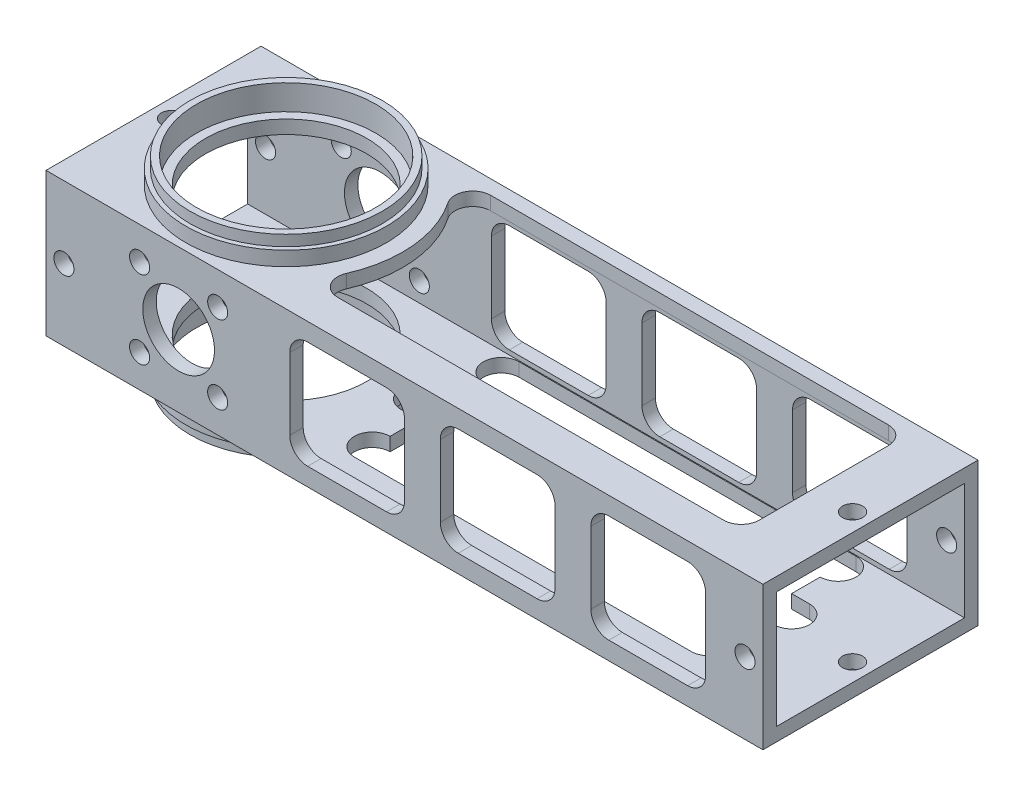
SolidWorks part; units mm, degrees
material "6061 Alloy"
ref_plane "Front Plane" through (0, 0, 0) normal (0, 0, 1) x (1, 0, 0)
ref_plane "Top Plane" through (0, 0, 0) normal (0, 1, 0) x (1, 0, 0)
ref_plane "Right Plane" through (0, 0, 0) normal (1, 0, 0) x (0, 0, -1)
sketch "Sketch1" plane through (0, 0, 0) normal (1, 0, 0) x (0, 0, -1)
  line L0 (2.3813, 23.0187) -> (35.7188, 23.0187)
  line L1 (0, 0) -> (38.1, 0)
  line L2 (0, 0) -> (0, 25.4)
  line L3 (0, 25.4) -> (38.1, 25.4)
  line L4 (38.1, 0) -> (38.1, 25.4)
  line L5 (35.7188, 2.3813) -> (35.7188, 23.0187)
  line L6 (2.3813, 2.3813) -> (35.7188, 2.3813)
  line L7 (2.3813, 2.3813) -> (2.3813, 23.0187)
  dimension "D1" = 38.1
  dimension "D2" = 25.4
  dimension "D3" = 2.3813
extrude "Boss-Extrude1" add sketch "Sketch1" along normal blind 127
sketch "Sketch2" plane through (0, 25.4, 0) normal (0, 1, 0) x (1, 0, 0)
  line L0 (0, 19.05) -> (23.495, 19.05) construction
  line L1 (0, 38.1) -> (0, 0) construction
  circle A0 centre (23.495, 19.05) radius 14.2875
  dimension "D2" = 28.575
  dimension "D1" = 23.495
extrude "Cut-Extrude1" cut sketch "Sketch2" against normal through all
sketch "Sketch3" plane through (0, 0, 0) normal (0, 0, 1) x (1, 0, 0)
  line L0 (0, 12.7) -> (23.495, 12.7) construction
  line L1 (0, 25.4) -> (0, 0) construction
  line L2 (0, 25.4) -> (23.495, 25.4) construction
  line L3 (63.5, 22.225) -> (69.85, 22.225) construction
  line L4 (16.5802, 5.7852) -> (30.4098, 5.7852) construction
  line L5 (16.5802, 5.7852) -> (16.5802, 19.6148) construction
  line L6 (16.5802, 19.6148) -> (30.4098, 19.6148) construction
  line L7 (30.4098, 5.7852) -> (30.4098, 19.6148) construction
  line L8 (16.5802, 5.7852) -> (30.4098, 19.6148) construction
  line L9 (16.5802, 19.6148) -> (30.4098, 5.7852) construction
  line L10 (46.355, 22.225) -> (60.325, 22.225)
  line L11 (43.18, 19.05) -> (43.18, 6.35)
  line L12 (46.355, 3.175) -> (60.325, 3.175)
  line L13 (63.5, 19.05) -> (63.5, 6.35)
  line L14 (73.025, 22.225) -> (86.995, 22.225)
  line L15 (69.85, 19.05) -> (69.85, 6.35)
  line L16 (73.025, 3.175) -> (86.995, 3.175)
  line L17 (90.17, 19.05) -> (90.17, 6.35)
  line L18 (99.695, 22.225) -> (113.665, 22.225)
  line L19 (96.52, 19.05) -> (96.52, 6.35)
  line L20 (99.695, 3.175) -> (113.665, 3.175)
  line L21 (116.84, 19.05) -> (116.84, 6.35)
  line L22 (90.17, 22.225) -> (96.52, 22.225) construction
  line L23 (127, 12.7) -> (116.84, 12.7) construction
  line L24 (127, 25.4) -> (127, 0) construction
  circle A0 centre (23.495, 12.7) radius 6.35
  circle A1 centre (16.5802, 19.6148) radius 1.778
  circle A2 centre (16.5802, 5.7852) radius 1.778
  circle A3 centre (30.4098, 5.7852) radius 1.778
  circle A4 centre (30.4098, 19.6148) radius 1.778
  arc A5 (113.665, 22.225) -> (116.84, 19.05) centre (113.665, 19.05) cw
  arc A6 (113.665, 3.175) -> (116.84, 6.35) centre (113.665, 6.35) ccw
  arc A7 (96.52, 6.35) -> (99.695, 3.175) centre (99.695, 6.35) ccw
  arc A8 (99.695, 22.225) -> (96.52, 19.05) centre (99.695, 19.05) ccw
  arc A9 (86.995, 22.225) -> (90.17, 19.05) centre (86.995, 19.05) cw
  arc A10 (86.995, 3.175) -> (90.17, 6.35) centre (86.995, 6.35) ccw
  arc A11 (69.85, 6.35) -> (73.025, 3.175) centre (73.025, 6.35) ccw
  arc A12 (73.025, 22.225) -> (69.85, 19.05) centre (73.025, 19.05) ccw
  arc A13 (60.325, 22.225) -> (63.5, 19.05) centre (60.325, 19.05) cw
  arc A14 (60.325, 3.175) -> (63.5, 6.35) centre (60.325, 6.35) ccw
  arc A15 (43.18, 6.35) -> (46.355, 3.175) centre (46.355, 6.35) ccw
  arc A16 (46.355, 22.225) -> (43.18, 19.05) centre (46.355, 19.05) ccw
  point P33 (116.84, 22.225)
  point P36 (116.84, 3.175)
  dimension "D1" = 12.7
  dimension "D3" = 3.556
  dimension "D8" = 3.175
  dimension "D2" = 19.558
  dimension "D4" = 20.32
  dimension "D5" = 19.05
  dimension "D6" = 6.35
  dimension "D7" = 10.16
extrude "Cut-Extrude2" cut sketch "Sketch3" against normal through all
sketch "Sketch4" plane through (0, 25.4, 0) normal (0, 1, 0) x (1, 0, 0)
  line L0 (45.3195, 6.35) -> (113.665, 6.35)
  line L1 (116.84, 9.525) -> (116.84, 32.385)
  line L2 (113.665, 35.56) -> (43.2235, 35.56)
  line L3 (116.84, 19.05) -> (127, 19.05) construction
  line L4 (127, 38.1) -> (127, 0) construction
  line L5 (127, 0) -> (116.84, 0) construction
  line L6 (127, 38.1) -> (0, 38.1) construction
  line L7 (127, 0) -> (0, 0) construction
  line L8 (79.4923, 6.35) -> (79.4923, 35.56) construction
  arc A0 (42.4096, 10.795) -> (40.593, 30.607) centre (23.495, 19.05) ccw
  circle A1 centre (23.495, 19.05) radius 14.2875 construction
  arc A2 (113.665, 6.35) -> (116.84, 9.525) centre (113.665, 9.525) ccw
  arc A3 (116.84, 32.385) -> (113.665, 35.56) centre (113.665, 32.385) ccw
  arc A4 (40.593, 30.607) -> (43.2235, 35.56) centre (43.2235, 32.385) cw
  arc A5 (42.4096, 10.795) -> (45.3195, 6.35) centre (45.3195, 9.525) ccw
  dimension "D3" = 6.35
  dimension "D4" = 3.175
  dimension "D1" = 2.54
  dimension "D2" = 6.35
extrude "Cut-Extrude3" cut sketch "Sketch4" against normal up to next
hole_wizard "#4 (0.209) Diameter Hole1" positions "3DSketch1" profile "Sketch5" hole size "#4" standard "ANSI Inch" end condition up to next
sketch3d "3DSketch1"
  line L0 (127, 25.4, -19.05) -> (123.825, 25.4, -19.05) construction
  line L1 (127, 25.4, -38.1) -> (127, 25.4, 0) construction
  line L6 (127, 12.7, 0) -> (123.825, 12.7, 0) construction
  line L7 (127, 25.4, 0) -> (127, 0, 0) construction
  line L13 (0, 25.4, -19.05) -> (3.175, 25.4, -19.05) construction
  line L14 (0, 25.4, -38.1) -> (0, 25.4, 0) construction
  line L17 (0, 12.7, 0) -> (3.175, 12.7, 0) construction
  line L18 (0, 25.4, 0) -> (0, 0, 0) construction
  point P13 (123.825, 12.7, 0)
  point P24 (3.175, 25.4, -19.05)
  point P30 (3.175, 12.7, 0)
  point P48 (3.175, 25.4, -19.05)
  point P67 (3.175, 25.4, -19.05)
  point P69 (3.175, 12.7, 0)
  point P77 (123.825, 25.4, -19.05)
  point P79 (123.825, 12.7, 0)
  point P81 (123.825, 0, -19.05)
  point P83 (123.825, 12.7, -38.1)
  point P90 (3.175, 12.7, -38.1)
  point P92 (3.175, 0, -19.05)
  dimension "D1" = 3.175
sketch "Sketch5" plane through (3.175, 25.4, -19.05) normal (1, 0, 0) x (0, 0, 1)
  line L0 (0, 0) -> (0, 2.3822)
  line L1 (0, 2.3822) -> (1.778, 2.3822)
  line L2 (1.778, 2.3822) -> (1.778, 0)
  line L5 (1.778, 0) -> (0, 0)
  line L11 (0, -6.35) -> (0, 107.95) construction
  dimension "Thru Hole Dia." = 3.556
  dimension "Thru Hole Depth" = 2.3823
sketch "Sketch6" plane through (0, 0, 0) normal (0, -1, 0) x (1, 0, 0)
  line L0 (48.26, -35.56) -> (107.95, -35.56)
  line L1 (48.26, -6.35) -> (107.95, -6.35)
  line L2 (79.4923, -6.35) -> (79.4923, -35.56) construction
  line L3 (113.665, -35.56) -> (43.2235, -35.56) construction
  line L4 (127, 0) -> (127, -38.1) construction
  line L5 (48.26, -6.35) -> (48.26, -35.56) construction
  line L6 (107.95, -6.35) -> (107.95, -35.56) construction
  line L8 (107.95, -12.7) -> (107.95, -17.78)
  line L9 (107.95, -17.78) -> (111.125, -17.78)
  line L10 (107.95, -29.21) -> (107.95, -24.13)
  line L11 (107.95, -24.13) -> (111.125, -24.13)
  line L12 (48.26, -29.21) -> (48.26, -24.13)
  line L13 (48.26, -12.7) -> (48.26, -17.78)
  line L14 (48.26, -17.78) -> (45.085, -17.78)
  line L15 (48.26, -24.13) -> (45.085, -24.13)
  arc A0 (107.95, -6.35) -> (107.95, -12.7) centre (107.95, -9.525) cw
  arc A1 (107.95, -35.56) -> (107.95, -29.21) centre (107.95, -32.385) ccw
  arc A2 (48.26, -35.56) -> (48.26, -29.21) centre (48.26, -32.385) cw
  arc A3 (48.26, -6.35) -> (48.26, -12.7) centre (48.26, -9.525) ccw
  arc A5 (111.125, -17.78) -> (111.125, -24.13) centre (111.125, -20.955) cw
  arc A6 (45.085, -17.78) -> (45.085, -24.13) centre (45.085, -20.955) ccw
  dimension "D1" = 59.69
  dimension "D2" = 3.175
  dimension "D3" = 3.175
  dimension "D4" = 19.05
extrude "Cut-Extrude4" cut sketch "Sketch6" against normal up to next
ref_plane "Plane1" through (0, 0, -19.05) normal (0, 0, 1) x (1, 0, 0)
sketch "Sketch7" plane through (0, 0, -19.05) normal (0, 0, 1) x (1, 0, 0)
  line L0 (23.495, -4.445) -> (23.495, 29.845) construction
  line L1 (39.37, 29.845) -> (39.37, 25.4)
  line L2 (39.37, 25.4) -> (41.275, 25.4)
  line L3 (41.275, 25.4) -> (41.275, 27.94)
  line L4 (41.275, 27.94) -> (40.513, 27.94)
  line L5 (40.513, 27.94) -> (40.513, 29.845)
  line L6 (40.513, 29.845) -> (39.37, 29.845)
  line L7 (39.37, -4.445) -> (39.37, 0)
  line L12 (39.37, 0) -> (41.275, 0)
  line L13 (41.275, 0) -> (41.275, -2.54)
  line L14 (41.275, -2.54) -> (40.513, -2.54)
  line L15 (40.513, -2.54) -> (40.513, -4.445)
  line L16 (40.513, -4.445) -> (39.37, -4.445)
  line L17 (127, 25.4) -> (0, 25.4) construction
  dimension "D1" = 35.56
  dimension "D2" = 31.75
  dimension "D3" = 34.036
  dimension "D4" = 4.445
  dimension "D5" = 2.54
revolve "Revolve1" add sketch "Sketch7" angle 360 about L0
